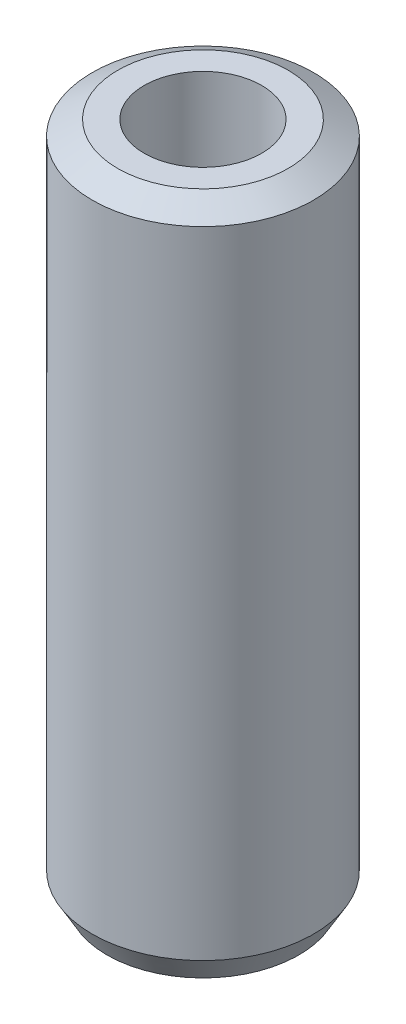
SolidWorks part; units mm, degrees
ref_plane "Front Plane" through (0, 0, 0) normal (0, 0, 1) x (1, 0, 0)
ref_plane "Top Plane" through (0, 0, 0) normal (0, 1, 0) x (1, 0, 0)
ref_plane "Right Plane" through (0, 0, 0) normal (1, 0, 0) x (0, 0, -1)
sketch "Sketch1" plane through (0, 0, 0) normal (0, 1, 0) x (1, 0, 0)
  circle A0 centre (0, 0) radius 30
  dimension "SHAFT_OD" = 60
extrude "Boss-Extrude1" add sketch "Sketch1" along normal blind 183.2506
sketch "Sketch2" plane through (0, 0, 0) normal (0, 1, 0) x (1, 0, 0)
  circle A0 centre (0, 0) radius 15.946
  dimension "BORE_D" = 31.8921
extrude "Cut-Extrude1" cut sketch "Sketch2" along normal through all
chamfer "Chamfer1" distance 3.9843 angle 60 2 edges at (0, 183.2506, 30) (0, 0, 30) first distance on face at (0, 183.2506, 30) first distance on face at (0, 0, 15.946)
